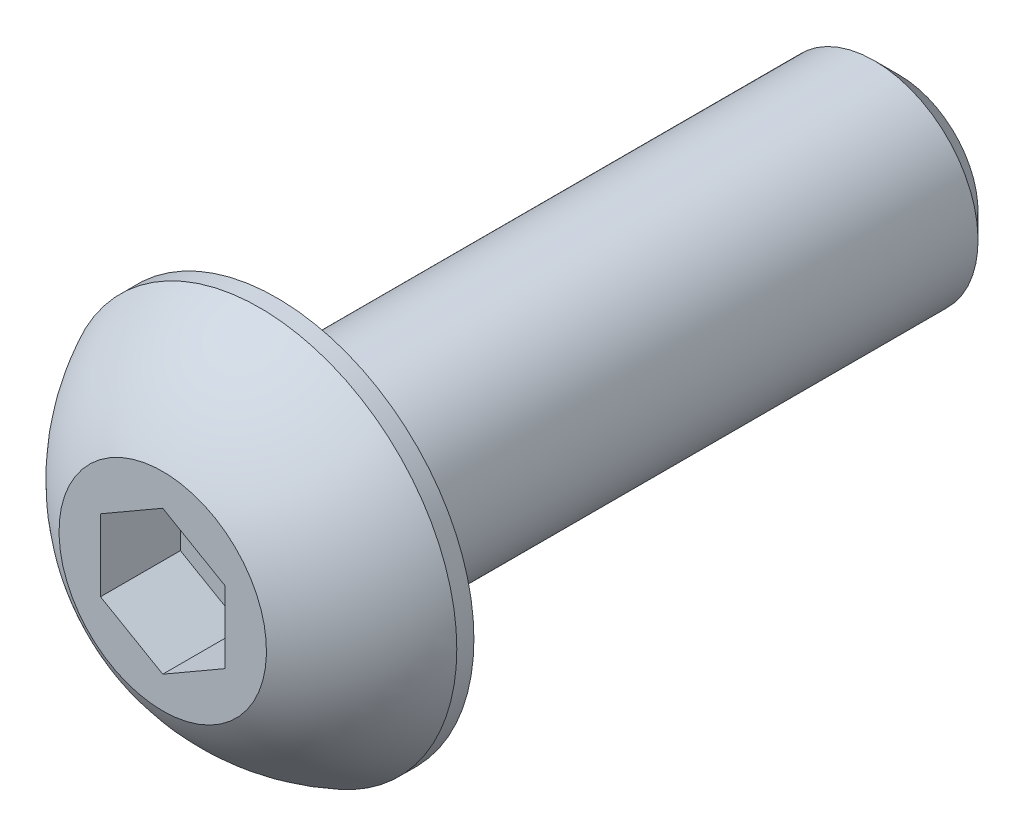
SolidWorks part; units mm, degrees
ref_plane "Front" through (0, 0, 0) normal (0, 0, 1) x (1, 0, 0)
ref_plane "Top" through (0, 0, 0) normal (0, 1, 0) x (1, 0, 0)
ref_plane "Right" through (0, 0, 0) normal (1, 0, 0) x (0, 0, -1)
sketch "Sketch1" plane through (0, 0, 0) normal (1, 0, 0) x (0, 0, -1)
  line L2 (2.75, 2.5) -> (17.75, 2.5)
  line L3 (17.75, 2.5) -> (17.75, 0)
  line L4 (17.75, 0) -> (2.75, 0)
  line L6 (2.3375, 4.75) -> (2.75, 4.75) construction
  line L7 (17.75, 2.5) -> (17.75, -2.5) construction
  line L8 (0, 0) -> (2.75, 0) construction
  line L9 (2.75, 4.75) -> (2.75, -4.75) construction
  line L11 (2.75, 2.5) -> (2.75, 0)
  line L13 (0, 1.5) -> (0, -1.5) construction
  line L14 (0, 1.5) -> (0, 2.5) construction
  arc A3 (0, 2.5) -> (2.3375, 4.75) centre (4.6581, 0) cw construction
  dimension "D1" = 0.4125
revolve "Revolve1" add sketch "Sketch1" angle 360 mid plane about L4
sketch "Sketch3" plane through (0, 0, -17.75) normal (0, 0, -1) x (-1, 0, 0)
  circle A0 centre (0, 0) radius 2.5
curve "Helix/Spiral1" [suppressed] pitch 0.8 height 15.8 turns 19.75
sketch "Sketch2" plane through (0, 0, 0) normal (1, 0, 0) x (0, 0, -1)
  line L0 (17.75, 2.5) -> (18.45, 2.5)
  line L1 (18.45, 2.5) -> (18.15, 1.9804)
  line L2 (18.15, 1.9804) -> (18.05, 1.9804)
  line L3 (18.05, 1.9804) -> (17.75, 2.5)
  line L4 (17.9, 2.2402) -> (18.3, 2.2402) construction
  dimension "D1" = 60
  dimension "D2" = 0.1
  dimension "D3" = 0.4
chamfer "Chamfer1" distance 0.6 angle 45 1 edges at (0, 2.5, -17.75)
sweep "Cut-Sweep1" [suppressed] cut profiles "Sketch2" path "Helix/Spiral1"
sketch "Sketch7" plane through (0, 0, 0) normal (1, 0, 0) x (0, 0, -1)
  line L6 (2.3375, 4.75) -> (2.75, 4.75) construction
  line L8 (0, 0) -> (2.75, 0) construction
  line L11 (2.75, 4.75) -> (2.75, -4.75) construction
  line L12 (2.3375, 4.75) -> (2.75, 4.75)
  line L13 (0, 0) -> (2.75, 0)
  line L14 (0, 1.5) -> (0, -1.5) construction
  line L15 (2.75, 4.75) -> (2.75, 0)
  line L16 (0, 2.5) -> (0, 0)
  arc A2 (2.3375, 4.75) -> (0, 2.5) centre (4.6581, 0) ccw construction
  arc A3 (2.3375, 4.75) -> (0, 2.5) centre (4.6581, 0) ccw
revolve "Revolve2" add sketch "Sketch7" angle 360 mid plane about L13
sketch "Sketch5" plane through (0, 0, 0) normal (0, 0, 1) x (1, 0, 0)
  line L1 (1.5, -0.866) -> (1.5, 0.866)
  line L2 (1.5, 0.866) -> (0, 1.7321)
  line L3 (0, 1.7321) -> (-1.5, 0.866)
  line L4 (-1.5, 0.866) -> (-1.5, -0.866)
  line L5 (-1.5, -0.866) -> (0, -1.7321)
  line L6 (0, -1.7321) -> (1.5, -0.866)
  circle A0 centre (0, 0) radius 1.5 construction
extrude "Cut-Extrude2" cut sketch "Sketch5" against normal blind 1.925
sketch "Sketch6" plane through (0, 0, 0) normal (0, 0, 1) x (1, 0, 0)
  circle A0 centre (0, 0) radius 1.7321
extrude "Cut-Extrude3" [suppressed] cut sketch "Sketch6" against normal blind 1.925 draft 45
sketch "Sketch9" [suppressed] plane through (0, 0, -6.6) normal (0, 0, 1) x (1, 0, 0)
  circle A2 centre (0, 0) radius 6
extrude "Boss-Extrude2" [suppressed] add sketch "Sketch9" against normal offset from surface (19 mm away) 32 up to face at (0, 1.9, -17.75)
sketch "Sketch10" plane through (0, 0, 0) normal (1, 0, 0) x (0, 0, -1)
  line L0 (17.75, 2.5) -> (17.75, -2.5) construction
  point P0 (16.55, -2.5)
  dimension "D1" = 1.2
equation "\"D3@Helix/Spiral1\" = \"Lg@Sketch1\" + \"D4@Helix/Spiral1\""
equation "\"D2@Sketch2\" = \"D4@Helix/Spiral1\" * .125"
equation "\"D3@Sketch2\" = \"D4@Helix/Spiral1\" * .5"
equation "\"D1@Chamfer1\" = \"D4@Helix/Spiral1\" * .75"
equation "\"D1@Cut-Extrude2\" = \"Head Ht@Sketch1\" * .7"
equation "\"D1@Sketch1\" = \"Head Ht@Sketch1\" * .15"
equation "\"D1@Sketch10\" = \"D4@Helix/Spiral1\" * 1.5"
equation "\"D1@Cut-Extrude3\" = \"D1@Cut-Extrude2\""
